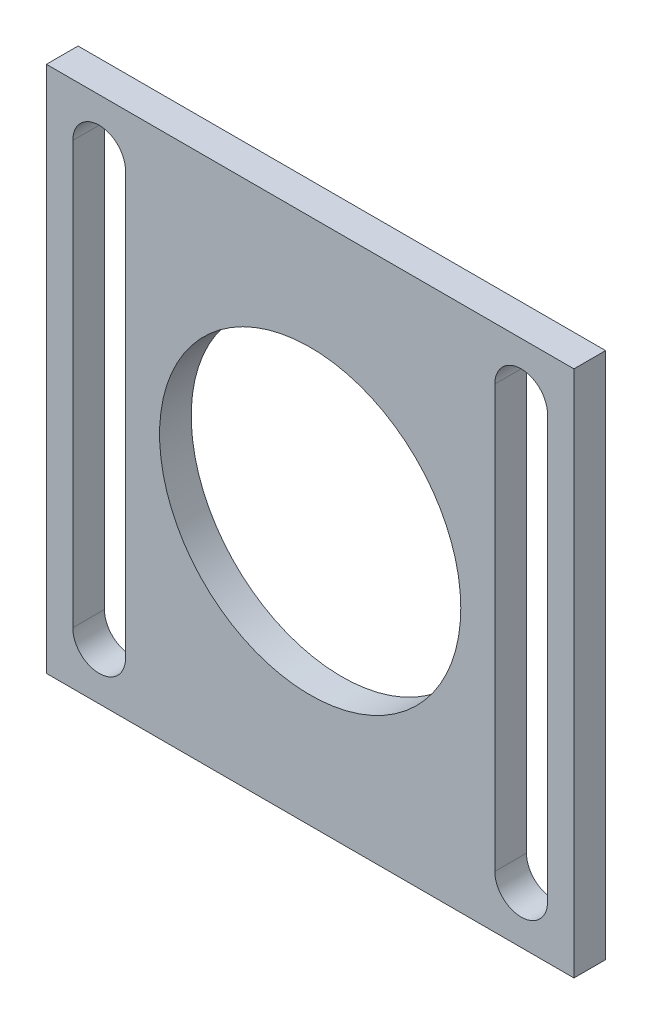
SolidWorks part; units mm, degrees
ref_plane "Front Plane" through (0, 0, 0) normal (0, 0, 1) x (1, 0, 0)
ref_plane "Top Plane" through (0, 0, 0) normal (0, 1, 0) x (1, 0, 0)
ref_plane "Right Plane" through (0, 0, 0) normal (1, 0, 0) x (0, 0, -1)
sketch "Sketch1" plane through (0, 0, 0) normal (0, 0, 1) x (1, 0, 0)
  line L1 (0, 0) -> (50, 0)
  line L2 (0, 0) -> (0, 50)
  line L3 (0, 50) -> (50, 50)
  line L4 (50, 0) -> (50, 50)
  dimension "D1" = 50
  dimension "D2" = 50
extrude "Boss-Extrude1" add sketch "Sketch1" along normal blind 3 contours L3 L4 L1 L2
sketch "Sketch2" plane through (0, 0, 3) normal (0, 0, 1) x (1, 0, 0)
  line L0 (25, 50) -> (25, 0) construction
  line L1 (0, 50) -> (50, 50) construction
  line L2 (0, 0) -> (50, 0) construction
  line L3 (0, 25) -> (50, 25) construction
  line L4 (0, 0) -> (0, 50) construction
  line L5 (50, 0) -> (50, 50) construction
  line L6 (5, 45) -> (5, 5) construction
  line L7 (7.5, 45) -> (7.5, 5)
  line L8 (2.5, 45) -> (2.5, 5)
  line L9 (45, 45) -> (45, 5) construction
  line L10 (47.5, 45) -> (47.5, 5)
  line L11 (42.5, 45) -> (42.5, 5)
  circle A0 centre (25, 25) radius 14.275
  arc A5 (7.5, 45) -> (2.5, 45) centre (5, 45) ccw
  arc A6 (2.5, 5) -> (7.5, 5) centre (5, 5) ccw
  arc A7 (47.5, 45) -> (42.5, 45) centre (45, 45) ccw
  arc A8 (42.5, 5) -> (47.5, 5) centre (45, 5) ccw
  point P22 (5, 25)
  point P27 (45, 25)
  dimension "D1" = 28.55
  dimension "D6" = 5
  dimension "D7" = 5
  dimension "D8" = 5
  dimension "D9" = 5
  dimension "D10" = 5
  dimension "D11" = 5
  dimension "D12" = 5
  dimension "D13" = 5
  dimension "D14" = 5
  dimension "D15" = 5
extrude "Cut-Extrude1" cut sketch "Sketch2" against normal blind 3
